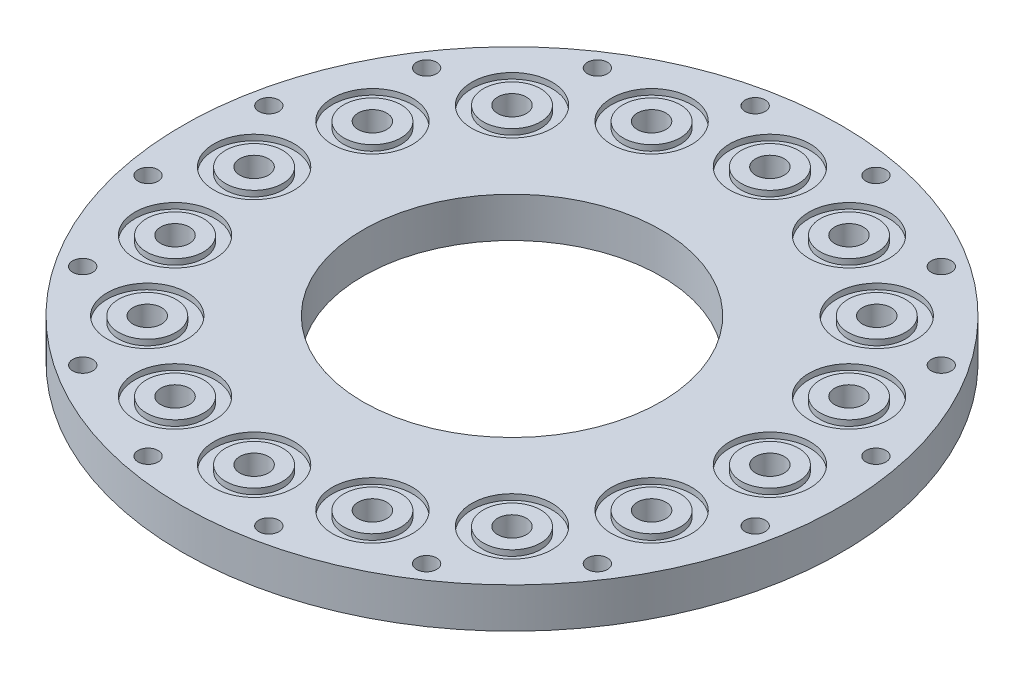
SolidWorks part; units mm, degrees
ref_plane "Front Plane" through (0, 0, 0) normal (0, 0, 1) x (1, 0, 0)
ref_plane "Top Plane" through (0, 0, 0) normal (0, 1, 0) x (1, 0, 0)
ref_plane "Right Plane" through (0, 0, 0) normal (1, 0, 0) x (0, 0, -1)
sketch "Sketch1" plane through (0, 0, 0) normal (0, 1, 0) x (1, 0, 0)
  line L0 (-10.5349, 52.9624) -> (0, 0) construction
  line L1 (0, 0) -> (62.7639, 0) construction
  line L2 (-17.2208, 41.5746) -> (0, 0) construction
  line L3 (0, 0) -> (0, 45) construction
  circle A0 centre (0, 0) radius 57.5
  circle A1 centre (0, 0) radius 54 construction
  circle A2 centre (-10.5349, 52.9624) radius 1.75
  circle A3 centre (10.5349, 52.9624) radius 1.75
  circle A4 centre (30.0008, 44.8994) radius 1.75
  circle A5 centre (44.8994, 30.0008) radius 1.75
  circle A6 centre (52.9624, 10.5349) radius 1.75
  circle A7 centre (52.9624, -10.5349) radius 1.75
  circle A8 centre (44.8994, -30.0008) radius 1.75
  circle A9 centre (30.0008, -44.8994) radius 1.75
  circle A10 centre (10.5349, -52.9624) radius 1.75
  circle A11 centre (-10.5349, -52.9624) radius 1.75
  circle A12 centre (-30.0008, -44.8994) radius 1.75
  circle A13 centre (-44.8994, -30.0008) radius 1.75
  circle A14 centre (0, 0) radius 26
  circle A15 centre (0, 0) radius 45 construction
  circle A16 centre (0, 45) radius 2.5
  circle A17 centre (17.2208, 41.5746) radius 2.5
  circle A18 centre (31.8198, 31.8198) radius 2.5
  circle A19 centre (41.5746, 17.2208) radius 2.5
  circle A20 centre (45, 0) radius 2.5
  circle A21 centre (41.5746, -17.2208) radius 2.5
  circle A22 centre (31.8198, -31.8198) radius 2.5
  circle A23 centre (17.2208, -41.5746) radius 2.5
  circle A24 centre (0, -45) radius 2.5
  circle A25 centre (-17.2208, -41.5746) radius 2.5
  circle A26 centre (-31.8198, -31.8198) radius 2.5
  circle A27 centre (-41.5746, -17.2208) radius 2.5
  circle A28 centre (-45, 0) radius 2.5
  circle A29 centre (-41.5746, 17.2208) radius 2.5
  circle A30 centre (-31.8198, 31.8198) radius 2.5
  circle A31 centre (-17.2208, 41.5746) radius 2.5
  circle A32 centre (-52.9624, -10.5349) radius 1.75
  circle A33 centre (-52.9624, 10.5349) radius 1.75
  circle A34 centre (-44.8994, 30.0008) radius 1.75
  circle A35 centre (-30.0008, 44.8994) radius 1.75
  point P31 (0, 0)
  point P55 (0, 0)
  dimension "D1" = 115
  dimension "D2" = 108
  dimension "D3" = 3.5
  dimension "D4" = 52
  dimension "D5" = 90
  dimension "D6" = 5
  dimension "D9" = 11.25
  dimension "D10" = 11.25
  dimension "D8" = 16
  dimension "D7" = 16
extrude "Boss-Extrude1" add sketch "Sketch1" along normal blind 7
sketch "Sketch2" plane through (0, 7, 0) normal (0, 1, 0) x (1, 0, 0)
  circle A0 centre (0, 0) radius 45 construction
  circle A1 centre (0, 45) radius 7
  circle A2 centre (17.2208, 41.5746) radius 7
  circle A3 centre (31.8198, 31.8198) radius 7
  circle A4 centre (41.5746, 17.2208) radius 7
  circle A5 centre (45, 0) radius 7
  circle A6 centre (41.5746, -17.2208) radius 7
  circle A7 centre (31.8198, -31.8198) radius 7
  circle A8 centre (17.2208, -41.5746) radius 7
  circle A9 centre (0, -45) radius 7
  circle A10 centre (-17.2208, -41.5746) radius 7
  circle A11 centre (-31.8198, -31.8198) radius 7
  circle A12 centre (0, 45) radius 5
  circle A13 centre (17.2208, 41.5746) radius 5
  circle A14 centre (31.8198, 31.8198) radius 5
  circle A15 centre (41.5746, 17.2208) radius 5
  circle A16 centre (45, 0) radius 5
  circle A17 centre (41.5746, -17.2208) radius 5
  circle A18 centre (31.8198, -31.8198) radius 5
  circle A19 centre (17.2208, -41.5746) radius 5
  circle A20 centre (0, -45) radius 5
  circle A21 centre (-17.2208, -41.5746) radius 5
  circle A22 centre (-31.8198, -31.8198) radius 5
  circle A23 centre (-41.5746, -17.2208) radius 5
  circle A24 centre (-45, 0) radius 5
  circle A25 centre (-41.5746, 17.2208) radius 5
  circle A26 centre (-31.8198, 31.8198) radius 5
  circle A27 centre (-17.2208, 41.5746) radius 5
  circle A28 centre (-41.5746, -17.2208) radius 7
  circle A29 centre (-45, 0) radius 7
  circle A30 centre (-41.5746, 17.2208) radius 7
  circle A31 centre (-31.8198, 31.8198) radius 7
  circle A32 centre (-17.2208, 41.5746) radius 7
  point P28 (0, 0)
  point P51 (0, 0)
  dimension "D1" = 14
  dimension "D3" = 10
  dimension "D2" = 16
  dimension "D4" = 16
extrude "Cut-Extrude1" cut sketch "Sketch2" against normal blind 1
